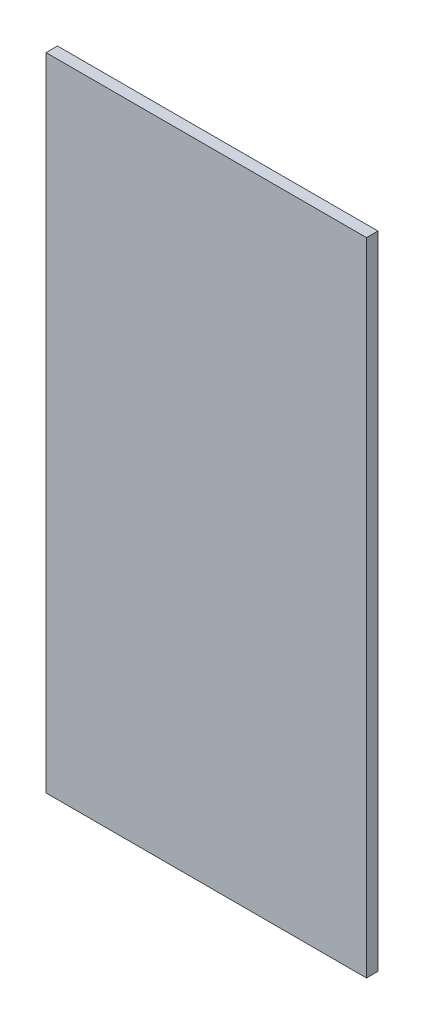
SolidWorks part; units mm, degrees
ref_plane "Front Plane" through (0, 0, 0) normal (0, 0, 1) x (1, 0, 0)
ref_plane "Top Plane" through (0, 0, 0) normal (0, 1, 0) x (1, 0, 0)
ref_plane "Right Plane" through (0, 0, 0) normal (1, 0, 0) x (0, 0, -1)
sketch "Sketch1" plane through (0, 0, 0) normal (0, 0, 1) x (1, 0, 0)
  line L8 (266.573, 7002.78) -> (-266.573, 7002.78)
  line L9 (-266.573, 7002.78) -> (-266.573, 5935.98)
  line L10 (-266.573, 5935.98) -> (266.573, 5935.98)
  line L11 (266.573, 5935.98) -> (266.573, 7002.78)
  point P2 (0, 7002.78)
  dimension "D1" = 1066.8
  dimension "D2" = 533.146
extrude "Boss-Extrude1" add sketch "Sketch1" against normal blind 19.05
